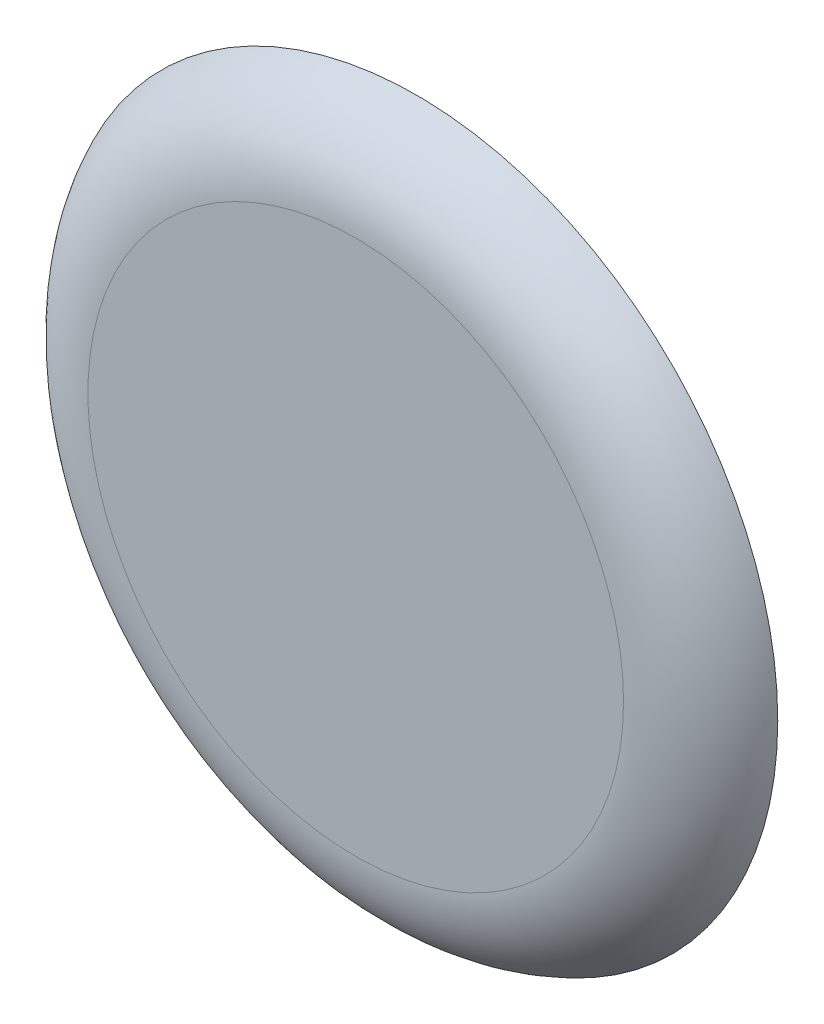
SolidWorks part; units mm, degrees
ref_plane "Přední rovina" through (0, 0, 0) normal (0, 0, 1) x (1, 0, 0)
ref_plane "Horní rovina" through (0, 0, 0) normal (0, 1, 0) x (1, 0, 0)
ref_plane "Pravá rovina" through (0, 0, 0) normal (1, 0, 0) x (0, 0, -1)
sketch "Sketch1" plane through (0, 0, 0) normal (0, 0, 1) x (1, 0, 0)
  circle A0 centre (0, 0) radius 17.75
  dimension "D1" = 35.5
extrude "Boss-Extrude1" add sketch "Sketch1" along normal blind 3
fillet "Fillet1" radius 5 1 edges at (17.75, 0, 3)
sketch "Sketch3" plane through (0, 0, 0) normal (0, 0, -1) x (1, 0, 0)
  circle A0 centre (0, 0) radius 3.175
  circle A1 centre (0, 5) radius 2.05
  circle A2 centre (0, 10) radius 2.05
  circle A9 centre (5, 0) radius 2.05
  circle A10 centre (10, 0) radius 2.05
  circle A11 centre (0, -5) radius 2.05
  circle A12 centre (0, -10) radius 2.05
  circle A13 centre (-5, 0) radius 2.05
  circle A14 centre (-10, 0) radius 2.05
  point P24 (-1.2398, -2.2452)
  dimension "D1" = 6.35
  dimension "D4" = 4.1
  dimension "D5" = 4.1
  dimension "D2" = 5
  dimension "D3" = 5
  dimension "D6" = 4
extrude "Cut-Extrude1" cut sketch "Sketch3" against normal blind 2 contours A0 A11 | A13 A0 A11 A9 A1 | A0 A11 | A10 | A12 | A0 A13 | A14 | A0 A1 | A0 A9 | A0 A13 | A0 A9 | A0 A1 | A2 region at (3.0674, 0, 0) region at (5.0332, 0, 0) region at (0, 0, 0) region at (0, -3.0674, 0) region at (0, -5.0332, 0) region at (0, 5.0332, 0) region at (0, 3.0674, 0) region at (-3.0674, 0, 0) region at (-5.0332, 0, 0) region at (10, 0, 0) region at (0, 10, 0) region at (-10, 0, 0)
